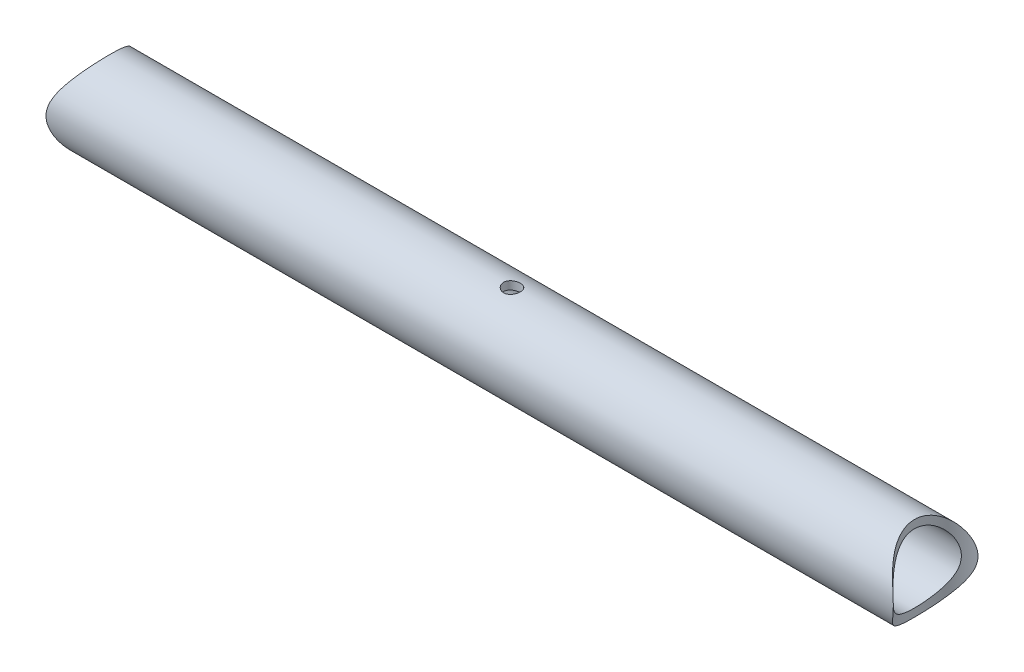
SolidWorks part; units mm, degrees
material "AISI 4130 Steel, annealed at 865C"
ref_plane "Front Plane" through (0, 0, 0) normal (0, 0, 1) x (1, 0, 0)
ref_plane "Top Plane" through (0, 0, 0) normal (0, 1, 0) x (1, 0, 0)
ref_plane "Right Plane" through (0, 0, 0) normal (1, 0, 0) x (0, 0, -1)
sketch "Sketch1" plane through (0, 0, 0) normal (1, 0, 0) x (0, 0, -1)
  circle A0 centre (0, 0) radius 12.7
  circle A1 centre (0, 0) radius 10.287
  dimension "D1" = 25.4
  dimension "D2" = 2.413
extrude "Boss-Extrude1" add sketch "Sketch1" along normal blind 135 and the other way blind 135
sketch "Sketch2" plane through (0, 0, 0) normal (0, 1, 0) x (1, 0, 0)
  line L0 (-136.525, 0) -> (136.525, 0) construction
  line L3 (-152.4, 43.0909) -> (152.4, 43.0909) construction
  line L4 (-152.4, 43.0909) -> (-152.4, -43.0909) construction
  line L5 (-152.4, -43.0909) -> (152.4, -43.0909) construction
  line L6 (152.4, 43.0909) -> (152.4, -43.0909) construction
  line L7 (-152.4, 43.0909) -> (152.4, -43.0909) construction
  line L8 (-152.4, -43.0909) -> (152.4, 43.0909) construction
  circle A0 centre (-136.525, 0) radius 15.875
  circle A1 centre (136.525, 0) radius 15.875
  circle A2 centre (0, 0) radius 2.5
  dimension "D1" = 31.75
  dimension "D2" = 5
  dimension "D3" = 304.8
  dimension "D4" = 273.05
extrude "Cut-Extrude1" cut sketch "Sketch2" against normal blind 25.4 and the other way blind 25.4
